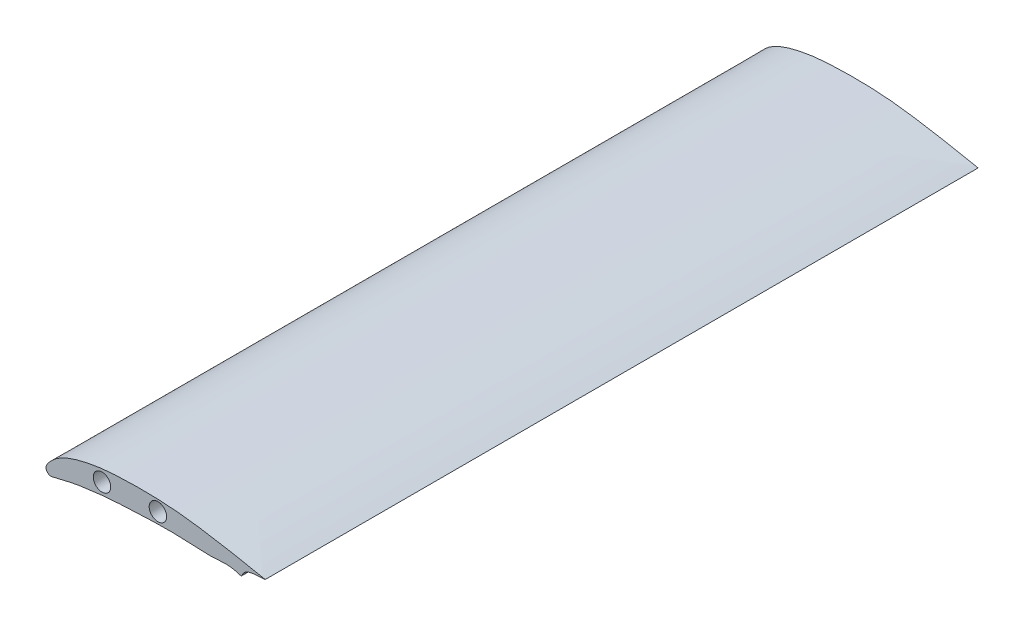
SolidWorks part; units mm, degrees
ref_plane "Front Plane" through (0, 0, 0) normal (0, 0, 1) x (1, 0, 0)
ref_plane "Top Plane" through (0, 0, 0) normal (0, 1, 0) x (1, 0, 0)
ref_plane "Right Plane" through (0, 0, 0) normal (1, 0, 0) x (0, 0, -1)
curve "cut"
  spline degree 3 poles (23.4129, 1.6732, 0) (26.2385, 1.4563, 0) (24.6666, 1.7296, 0) (24.0631, 1.8554, 0) (23.3676, 1.991, 0) (21.8468, 2.2963, 0) (19.449, 2.7181, 0) (16.2072, 3.2214, 0) (12.9484, 3.4695, 0) (9.6969, 3.4728, 0) (6.9821, 3.3475, 0) (4.8205, 2.9999, 0) (3.4681, 2.6661, 0) (2.3898, 2.2791, 0) (1.5621, 1.8808, 0) (0.8771, 1.387, 0) (0.3211, 0.7955, 0) (-0.2215, 0.1147, 0) (0.3268, -0.5439, 0) (0.9664, -0.4072, 0) (1.6227, -0.2531, 0) (2.4342, -0.0542, 0) (3.5055, 0.1899, 0) (4.8628, 0.367, 0) (7.0187, 0.6467, 0) (9.7247, 0.7989, 0) (12.9785, 0.9423, 0) (16.1932, 0.9351, 0) (19.4533, 0.6426, 0) (21.3272, 1.0151, 0) (22.681, 0.4934, 0) (22.872, 0.9133, 0) (23.4129, 1.6732, 0) (26.2385, 1.4563, 0) (24.6666, 1.7296, 0) knots -0.057358 -0.055858 -0.038892 0 0.013065 0.026125 0.039194 0.052259 0.114884 0.177154 0.238899 0.300426 0.362024 0.393129 0.424785 0.441092 0.458148 0.477061 0.488021 0.506046 0.517777 0.525474 0.541223 0.556994 0.572703 0.603759 0.634701 0.696322 0.75786 0.819389 0.880956 0.936472 0.942642 0.944142 0.961108 1 1.013065 1.026125 1.039194 periodic
sketch "cut sketch" plane through (0, 0, 0) normal (0, 0, 1) x (1, 0, 0)
  line L0 (0, 0) -> (19.8755, 0) construction
  line L1 (19.8755, 0) -> (19.8755, 1.2434) construction
  line L2 (9.9377, 0) -> (9.9377, 2.69) construction
  line L3 (198.755, 0) -> (198.755, 12.4341) construction
  line L4 (0, 0) -> (198.755, 0) construction
  line L5 (99.3775, 0) -> (99.3775, 26.9) construction
  line L6 (50.8, 0) -> (50.8, 4.4202) construction
  line L7 (50.8, 4.4202) -> (50.8, 25.4008) construction
  line L8 (101.6, 0) -> (101.6, 7.179) construction
  line L9 (101.6, 7.179) -> (101.6, 26.8197) construction
  circle A0 centre (50.8, 14.9105) radius 7.9375
  circle A1 centre (101.6, 16.9993) radius 7.9375
  spline S0 degree 3 poles (183.2058, 13.0927) (205.3166, 11.3957) (193.0163, 13.5342) (188.2941, 14.5185) (182.8517, 15.5792) (170.9511, 17.9689) (152.1886, 21.2695) (126.8211, 25.2077) (101.3214, 27.1488) (75.8786, 27.1749) (54.6349, 26.194) (37.7206, 23.4738) (27.1378, 20.8625) (18.6998, 17.8336) (12.2233, 14.7175) (6.8632, 10.853) (2.5126, 6.2248) (-1.7331, 0.8973) (2.5575, -4.2564) (7.562, -3.1865) (12.6976, -1.9802) (19.0475, -0.4243) (27.4305, 1.4859) (38.0511, 2.872) (54.9212, 5.0608) (76.096, 6.2515) (101.5566, 7.3732) (126.7117, 7.3174) (152.222, 5.0287) (166.8852, 7.9435) (177.4789, 3.8608) (178.9732, 7.1462) (183.2058, 13.0927) (205.3166, 11.3957) (193.0163, 13.5342) knots -0.057358 -0.055858 -0.038892 0 0.013065 0.026125 0.039194 0.052259 0.114884 0.177154 0.238899 0.300426 0.362024 0.393129 0.424785 0.441092 0.458148 0.477061 0.488021 0.506046 0.517777 0.525474 0.541223 0.556994 0.572703 0.603759 0.634701 0.696322 0.75786 0.819389 0.880956 0.936472 0.942642 0.944142 0.961108 1 1.013065 1.026125 1.039194 only from (198.755, 12.4341) to (198.755, 12.4341)
  spline S2 degree 3 poles (18.3206, 1.3093) (20.5317, 1.1396) (19.3016, 1.3534) (18.8294, 1.4518) (18.2852, 1.5579) (17.0951, 1.7969) (15.2189, 2.1269) (12.6821, 2.5208) (10.1321, 2.7149) (7.5879, 2.7175) (5.4635, 2.6194) (3.7721, 2.3474) (2.7138, 2.0862) (1.87, 1.7834) (1.2223, 1.4718) (0.6863, 1.0853) (0.2513, 0.6225) (-0.1733, 0.0897) (0.2558, -0.4256) (0.7562, -0.3186) (1.2698, -0.198) (1.9047, -0.0424) (2.743, 0.1486) (3.8051, 0.2872) (5.4921, 0.5061) (7.6096, 0.6252) (10.1557, 0.7373) (12.6712, 0.7317) (15.2222, 0.5029) (16.6885, 0.7944) (17.7479, 0.3861) (17.8973, 0.7146) (18.3206, 1.3093) (20.5317, 1.1396) (19.3016, 1.3534) knots -0.057358 -0.055858 -0.038892 0 0.013065 0.026125 0.039194 0.052259 0.114884 0.177154 0.238899 0.300426 0.362024 0.393129 0.424785 0.441092 0.458148 0.477061 0.488021 0.506046 0.517777 0.525474 0.541223 0.556994 0.572703 0.603759 0.634701 0.696322 0.75786 0.819389 0.880956 0.936472 0.942642 0.944142 0.961108 1 1.013065 1.026125 1.039194 only from (19.8755, 1.2434) to (19.8755, 1.2434) construction
  point P11 (50.8, 0)
  point P17 (101.6, 0)
  point P20 (101.6, 16.9993)
  dimension "D8" = 15.875
  dimension "D10" = 15.875
  dimension "D1" = 1.2434
  dimension "D2" = 19.8755
  dimension "D3" = 2.69
  dimension "D4" = 198.755
  dimension "D5" = 12.4341
  dimension "D6" = 26.9
  dimension "D7" = 50.8
  dimension "D9" = 50.8
curve "full"
  spline degree 3 poles (25.4, 0.0889, 0) (24.9755, 0.1879, 0) (24.1284, 0.3854, 0) (22.4316, 0.7474, 0) (20.3056, 1.1527, 0) (17.7661, 1.6728, 0) (15.2225, 2.1285, 0) (12.6828, 2.5208, 0) (10.1333, 2.7153, 0) (7.5886, 2.7177, 0) (5.4641, 2.6194, 0) (3.7724, 2.3478, 0) (2.7142, 2.0863, 0) (1.8702, 1.7836, 0) (1.2225, 1.4719, 0) (0.6864, 1.0854, 0) (0.2512, 0.6226, 0) (-0.1733, 0.0898, 0) (0.2557, -0.4257, 0) (0.7562, -0.3188, 0) (1.2698, -0.1979, 0) (1.905, -0.0426, 0) (2.7433, 0.1487, 0) (3.8055, 0.2872, 0) (5.4925, 0.5064, 0) (7.6119, 0.6227, 0) (10.1512, 0.7472, 0) (12.6929, 0.6952, 0) (15.2354, 0.6324, 0) (17.7755, 0.4534, 0) (20.3173, 0.2785, 0) (22.4335, 0.1017, 0) (24.1313, 0.0327, 0) (24.9769, -0.0484, 0) (25.4, -0.0889, 0) knots 0 0 0 0 0.025045 0.049982 0.099693 0.149405 0.198931 0.248178 0.297011 0.345669 0.394384 0.418982 0.444018 0.456913 0.470405 0.485361 0.494029 0.508284 0.517562 0.523649 0.536105 0.548579 0.561002 0.585562 0.610033 0.658766 0.707435 0.756094 0.804785 0.853571 0.902386 0.951201 0.975578 1 1 1 1
sketch "full foil sketch" plane through (0, 0, 0) normal (0, 0, 1) x (1, 0, 0)
  line L0 (25.4, 0.0889) -> (25.4, -0.0889)
  spline S0 degree 3 poles (801.0896, 2896.6153) (93.9918, -50.1126) (62.4745, -7.7955) (22.4316, 0.7474) (20.3056, 1.1527) (17.7661, 1.6728) (15.2225, 2.1285) (12.6828, 2.5208) (10.1333, 2.7153) (7.5886, 2.7177) (5.4641, 2.6194) (3.7724, 2.3478) (2.7142, 2.0863) (1.8702, 1.7836) (1.2225, 1.4719) (0.6864, 1.0854) (0.2512, 0.6226) (-0.1733, 0.0898) (0.2557, -0.4257) (0.7562, -0.3188) (1.2698, -0.1979) (1.905, -0.0426) (2.7433, 0.1487) (3.8055, 0.2872) (5.4925, 0.5064) (7.6119, 0.6227) (10.1512, 0.7472) (12.6929, 0.6952) (15.2354, 0.6324) (17.7755, 0.4534) (20.3173, 0.2785) (22.4335, 0.1017) (51.136, -1.0652) (75.492, -52.2811) (315.1102, 2985.1217) knots -2.25291 -2.25291 -2.25291 -2.25291 0.025045 0.049982 0.099693 0.149405 0.198931 0.248178 0.297011 0.345669 0.394384 0.418982 0.444018 0.456913 0.470405 0.485361 0.494029 0.508284 0.517562 0.523649 0.536105 0.548579 0.561002 0.585562 0.610033 0.658766 0.707435 0.756094 0.804785 0.853571 0.902386 0.951201 0.975578 2.552608 2.552608 2.552608 2.552608 only from (25.4, 0.0889) to (25.4, -0.0889) construction
  spline S1 degree 3 poles (25.4, 0.0889) (24.9755, 0.1879) (24.1284, 0.3854) (22.4316, 0.7474) (20.3056, 1.1527) (17.7661, 1.6728) (15.2225, 2.1285) (12.6828, 2.5208) (10.1333, 2.7153) (7.5886, 2.7177) (5.4641, 2.6194) (3.7724, 2.3478) (2.7142, 2.0863) (1.8702, 1.7836) (1.2225, 1.4719) (0.6864, 1.0854) (0.2512, 0.6226) (-0.1733, 0.0898) (0.2557, -0.4257) (0.7562, -0.3188) (1.2698, -0.1979) (1.905, -0.0426) (2.7433, 0.1487) (3.8055, 0.2872) (5.4925, 0.5064) (7.6119, 0.6227) (10.1512, 0.7472) (12.6929, 0.6952) (15.2354, 0.6324) (17.7755, 0.4534) (20.3173, 0.2785) (22.4335, 0.1017) (24.1313, 0.0327) (24.9769, -0.0484) (25.4, -0.0889) knots 0 0 0 0 0.025045 0.049982 0.099693 0.149405 0.198931 0.248178 0.297011 0.345669 0.394384 0.418982 0.444018 0.456913 0.470405 0.485361 0.494029 0.508284 0.517562 0.523649 0.536105 0.548579 0.561002 0.585562 0.610033 0.658766 0.707435 0.756094 0.804785 0.853571 0.902386 0.951201 0.975578 1 1 1 1
extrude "Boss-Extrude1" add sketch "cut sketch" along normal blind 647.7
ref_plane "Plane1" through (0, 0, 323.85) normal (0, 0, 1) x (1, 0, 0)
sketch "Sketch1" plane through (0, 0, 323.85) normal (0, 0, 1) x (1, 0, 0)
  line L0 (177.2281, 4.2649) -> (177.2281, -23.5227) construction
  line L1 (177.2281, -23.5227) -> (184.8481, -23.5227) construction
  circle A0 centre (184.8481, -23.5227) radius 1.27
  spline S0 degree 3 poles (183.2058, 13.0927) (205.3166, 11.3957) (193.0163, 13.5342) (188.2941, 14.5185) (182.8517, 15.5792) (170.9511, 17.9689) (152.1886, 21.2695) (126.8211, 25.2077) (101.3214, 27.1488) (75.8786, 27.1749) (54.6349, 26.194) (37.7206, 23.4738) (27.1378, 20.8625) (18.6998, 17.8336) (12.2233, 14.7175) (6.8632, 10.853) (2.5126, 6.2248) (-1.7331, 0.8973) (2.5575, -4.2564) (7.562, -3.1865) (12.6976, -1.9802) (19.0475, -0.4243) (27.4305, 1.4859) (38.0511, 2.872) (54.9212, 5.0608) (76.096, 6.2515) (101.5566, 7.3732) (126.7117, 7.3174) (152.222, 5.0287) (166.8852, 7.9435) (177.4789, 3.8608) (178.9732, 7.1462) (183.2058, 13.0927) (205.3166, 11.3957) (193.0163, 13.5342) knots -0.057358 -0.055858 -0.038892 0 0.013065 0.026125 0.039194 0.052259 0.114884 0.177154 0.238899 0.300426 0.362024 0.393129 0.424785 0.441092 0.458148 0.477061 0.488021 0.506046 0.517777 0.525474 0.541223 0.556994 0.572703 0.603759 0.634701 0.696322 0.75786 0.819389 0.880956 0.936472 0.942642 0.944142 0.961108 1 1.013065 1.026125 1.039194 only from (198.755, 12.4341) to (198.755, 12.4341) construction
  point P0 (177.2281, 4.2649)
  dimension "D3" = 2.54
  dimension "D1" = 27.7876
  dimension "D2" = 7.62
